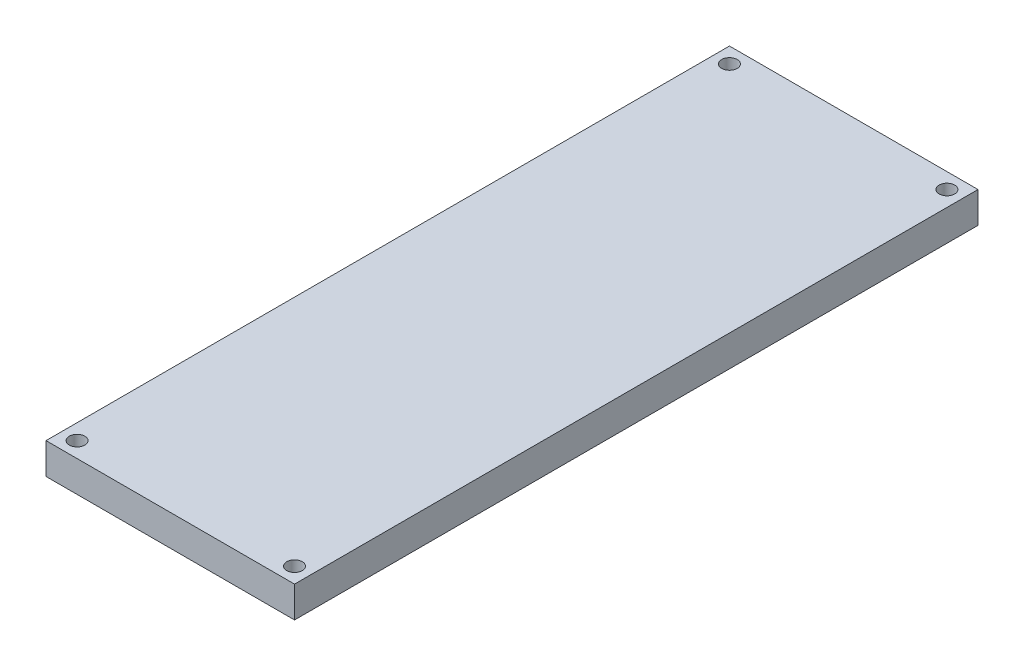
SolidWorks part; units mm, degrees
material "6061-T6 (SS)"
ref_plane "Front Plane" through (0, 0, 0) normal (0, 0, 1) x (1, 0, 0)
ref_plane "Top Plane" through (0, 0, 0) normal (0, 1, 0) x (1, 0, 0)
ref_plane "Right Plane" through (0, 0, 0) normal (1, 0, 0) x (0, 0, -1)
sketch "Sketch1" plane through (0, 0, 0) normal (0, 1, 0) x (1, 0, 0)
  line L0 (50.8, -139.7) -> (-50.8, -139.7)
  line L5 (50.8, -139.7) -> (50.8, 139.7)
  line L6 (50.8, 139.7) -> (-50.8, 139.7)
  line L7 (-50.8, -139.7) -> (-50.8, 139.7)
  line L8 (-50.8, 139.7) -> (50.8, -139.7) construction
  line L9 (50.8, 139.7) -> (-50.8, -139.7) construction
  point P4 (0, 0)
extrude "Base Shape" add sketch "Sketch1" along normal blind 12.7
sketch "Sketch2" plane through (0, 12.7, 0) normal (0, 1, 0) x (1, 0, 0)
  line L0 (0, 139.7) -> (0, -139.7) construction
  line L5 (50.8, 139.7) -> (-50.8, 139.7) construction
  line L8 (-50.8, -139.7) -> (50.8, -139.7) construction
  line L11 (-50.8, 0) -> (50.8, 0) construction
  line L12 (-50.8, 139.7) -> (-50.8, -139.7) construction
  line L13 (50.8, -139.7) -> (50.8, 139.7) construction
  line L14 (-50.8, -127) -> (-38.1, -139.7) construction
  line L15 (-50.8, -139.7) -> (-38.1, -139.7) construction
  line L16 (-50.8, -139.7) -> (-50.8, -127) construction
  line L17 (-50.8, -127) -> (-38.1, -127) construction
  line L18 (-38.1, -139.7) -> (-38.1, -127) construction
  circle A4 centre (-44.45, -133.35) radius 3.175
  circle A5 centre (44.45, -133.35) radius 3.175
  circle A6 centre (44.45, 133.35) radius 3.175
  circle A7 centre (-44.45, 133.35) radius 3.175
  dimension "D1" = 12.7
  dimension "D2" = 6.35
extrude "0.25\" Diameter Clearance Holes for Lid" cut sketch "Sketch2" against normal blind 12.7 contours A4 | A5 | A6 | A7 region at (-44.45, 12.7, 133.35) region at (44.45, 12.7, 133.35) region at (44.45, 12.7, -133.35) region at (-44.45, 12.7, -133.35)
equation "\"Pipe Diameter\"= 1in"
equation "\"Pipe Radial Distance\"= 3.01in"
equation "\"Rocket Diameter\"= 12in"
equation "\"Airframe Thickness\"= 0.125in"
equation "\"Arduino Mega Length\"= 101.52mm"
equation "\"Arduino Mega Width\"= 53.3mm"
equation "\"Interior Height\"= 2in"
equation "\"Wall Thickness\"= 0.5in"
equation "\"Assembly Hole Diameter\"= 0.25in"
equation "\"4-40 Standoff Depth\"= 0.1875in"
equation "\"Wire Hole Diameter\"= 0.1in"
equation "\"D1\"= \"Wall Thickness\""
equation "\"Lid Length\"= ( 2 * \"Wall Thickness\" ) + ( \"Arduino Mega Length\" * 1.25 )"
equation "\"Lid Width\"= ( 2 * \"Wall Thickness\" ) + ( \"Arduino Mega Width\" * 1.25 )"
equation "\"D1@Base Shape\" = \"Wall Thickness\""
equation "\"D1@Sketch2\"=\"Wall Thickness\""
equation "\"D2@Sketch2\"=\"Assembly Hole Diameter\""
